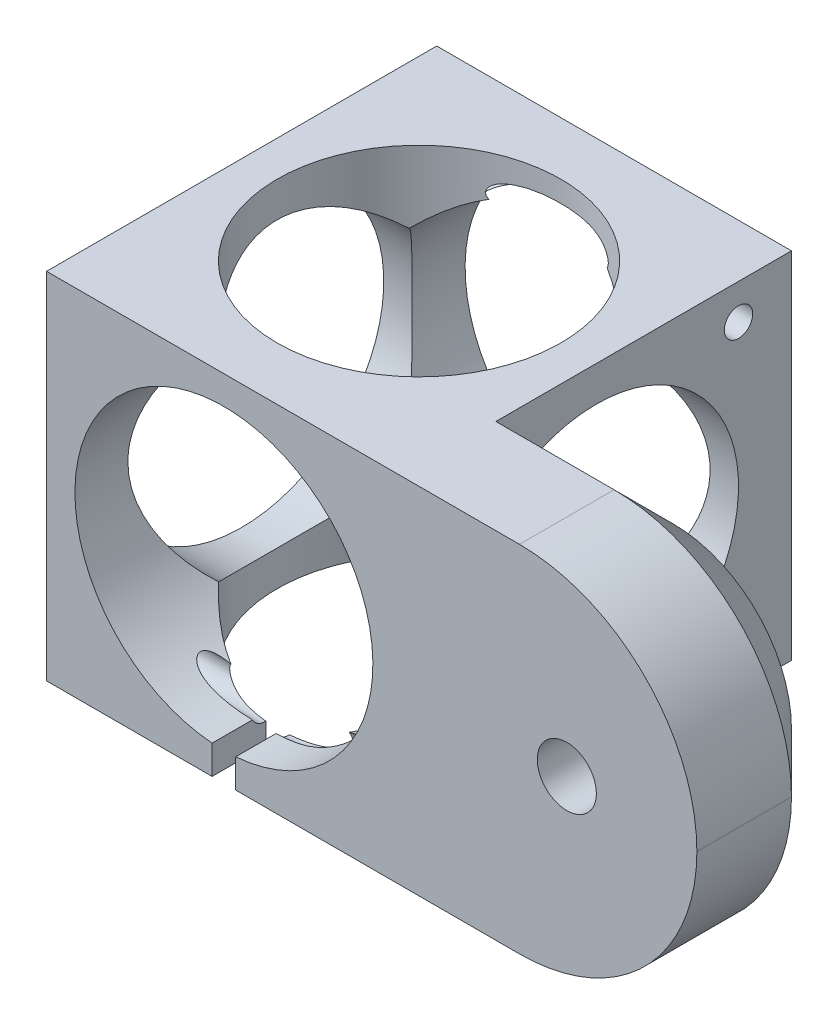
SolidWorks part; units mm, degrees
material "S235JR"
ref_plane "xy" through (0, 0, 0) normal (0, 0, 1) x (1, 0, 0)
ref_plane "xz" through (0, 0, 0) normal (0, 1, 0) x (1, 0, 0)
ref_plane "yz" through (0, 0, 0) normal (1, 0, 0) x (0, 0, -1)
ref_axis "x" through (-17.75, 0, 0) along (1, 0, 0)
ref_axis "y" through (0, 16.5, 0) along (0, -1, 0)
ref_axis "z" through (0, 0, -18.15) along (0, 0, 1)
sketch "Skizze1" plane through (0, 0, 0) normal (0, 0, 1) x (1, 0, 0)
  line L1 (-15, 15) -> (40, 15)
  line L2 (-15, 15) -> (-15, -15)
  line L3 (-15, -15) -> (40, -15)
  line L4 (40, 15) -> (40, -15)
  circle A0 centre (0, 0) radius 12.6
  circle A1 centre (29, 0) radius 2.5
  point P7 (40, 0)
  point P10 (0, 0)
  point P11 (30, -3.4766)
  dimension "D1" = 25.2
  dimension "D5" = 5
  dimension "D2" = 15
  dimension "D3" = 55
  dimension "D4" = 30
  dimension "D6" = 29
extrude "Aufsatz-Linear austragen1" add sketch "Skizze1" along normal mid plane 33
sketch "Skizze2" plane through (0, 0, 0) normal (0, 1, 0) x (1, 0, 0)
  line L1 (40, 16.5) -> (15, 16.5)
  line L2 (40, 16.5) -> (40, -3.5)
  line L3 (40, -3.5) -> (15, -3.5)
  line L4 (15, 16.5) -> (15, -3.5)
  dimension "D1" = 20
  dimension "D2" = 25
extrude "Schnitt-Linear austragen1" cut sketch "Skizze2" against normal through all and the other way through all
fillet "Verrundung1" radius 15 2 edges at (40, 15, 10) (40, -15, 10)
chamfer "Fase1" distance 5 angle 45 4 edges at (20, -15, 3.5) (20, 15, 3.5) (35.6066, -10.6066, 3.5) (35.6066, 10.6066, 3.5)
ref_plane "ZeilEbene1" through (29, 0, 0) normal (1, 0, 0) x (0, 0, -1)
sketch "Skizze3" plane through (-15, 0, 0) normal (-1, 0, 0) x (0, 0, 1)
  line L1 (-12.0208, -12.0208) -> (12.0208, -12.0208) construction
  line L2 (-12.0208, -12.0208) -> (-12.0208, 12.0208) construction
  line L3 (-12.0208, 12.0208) -> (12.0208, 12.0208) construction
  line L4 (12.0208, -12.0208) -> (12.0208, 12.0208) construction
  circle A0 centre (0, 0) radius 17 construction
  circle A1 centre (-12.0208, -12.0208) radius 1.2
  circle A2 centre (-12.0208, 12.0208) radius 1.2
  circle A3 centre (12.0208, 12.0208) radius 1.2
  circle A4 centre (12.0208, -12.0208) radius 1.2
  circle A5 centre (0, 0) radius 12.0208
  dimension "D1" = 34
  dimension "D2" = 2.4
extrude "Schnitt-Linear austragen2" cut sketch "Skizze3" against normal up to vertex (30 mm away) up to point (15, -15, -16.5)
sketch "Skizze4" plane through (0, 0, 0) normal (0, 0, 1) x (1, 0, 0)
  line L1 (-1, 0) -> (1, 0)
  line L2 (-1, 0) -> (-1, -21.6324)
  line L3 (-1, -21.6324) -> (1, -21.6324)
  line L4 (1, 0) -> (1, -21.6324)
  dimension "D1" = 2
extrude "Schnitt-Linear austragen3" cut sketch "Skizze4" against normal through all and the other way through all
chamfer "Fase2" distance 5 angle 45 1 edges at (15, 0, 3.5)
fillet "Verrundung2" radius 10 1 edges at (20, 0, 3.5)
sketch "Skizze5" plane through (0, 0, 0) normal (0, 1, 0) x (1, 0, 0)
  line L0 (15, 16.5) -> (-15, -16.5) construction
  circle A0 centre (0, 0) radius 12
  dimension "D1" = 24
extrude "Schnitt-Linear austragen4" cut sketch "Skizze5" against normal through all and the other way through all
